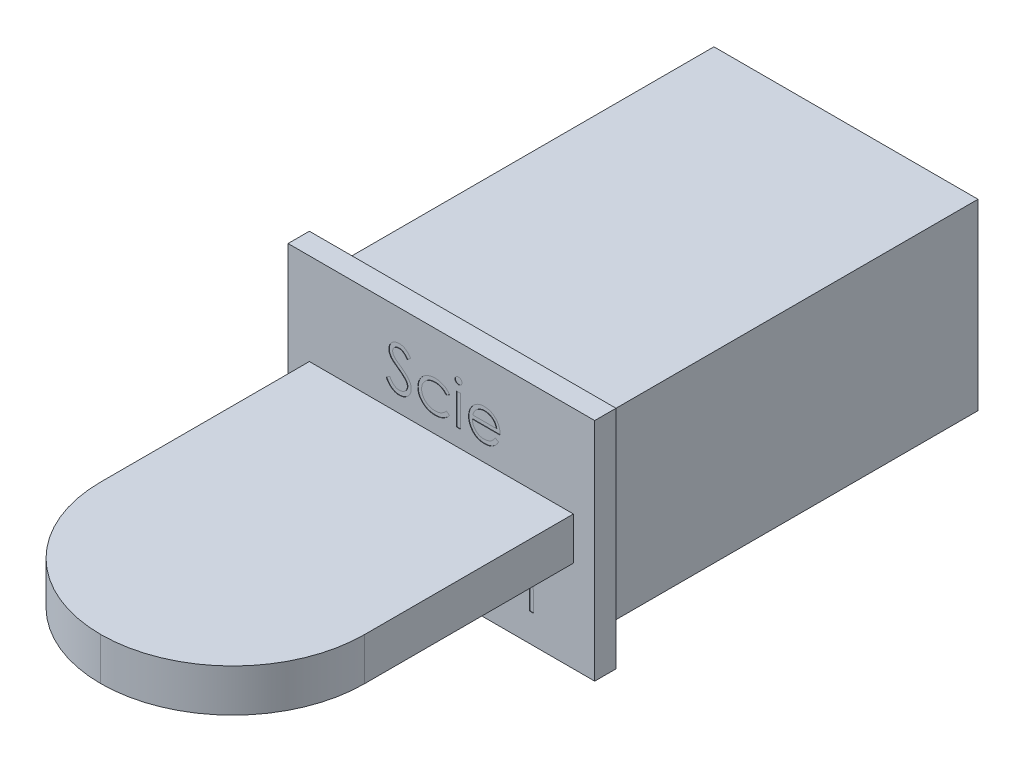
SolidWorks part; units mm, degrees
ref_plane "Front" through (0, 0, 0) normal (0, 0, 1) x (1, 0, 0)
ref_plane "Top" through (0, 0, 0) normal (0, 1, 0) x (1, 0, 0)
ref_plane "Right" through (0, 0, 0) normal (1, 0, 0) x (0, 0, -1)
sketch "Esquisse1" plane through (0, 0, 0) normal (0, 0, 1) x (1, 0, 0)
  line L1 (0, 0) -> (720, 0)
  line L2 (0, 0) -> (0, 530)
  line L3 (0, 530) -> (720, 530)
  line L4 (720, 0) -> (720, 530)
  dimension "D1" = 720
  dimension "D2" = 530
extrude "Boss.-Extru.1" add sketch "Esquisse1" along normal blind 50
sketch "Esquisse2" plane through (0, 0, 0) normal (0, 0, -1) x (-1, 0, 0)
  line L0 (-360, 480) -> (-360, 530) construction
  line L1 (-670, 480) -> (-50, 480)
  line L2 (-670, 480) -> (-670, 50)
  line L3 (-670, 50) -> (-50, 50)
  line L4 (-50, 480) -> (-50, 50)
  line L5 (-720, 530) -> (0, 530) construction
  line L6 (0, 0) -> (-720, 0) construction
  line L9 (-50, 265) -> (0, 265) construction
  line L10 (0, 530) -> (0, 0) construction
  dimension "D1" = 50
extrude "Boss.-Extru.2" add sketch "Esquisse2" along normal blind 900
sketch "Esquisse3" plane through (0, 0, 50) normal (0, 0, 1) x (1, 0, 0)
  line L0 (670, 265) -> (720, 265) construction
  line L1 (50, 215) -> (670, 215)
  line L2 (50, 215) -> (50, 315)
  line L3 (50, 315) -> (670, 315)
  line L4 (670, 215) -> (670, 315)
  line L5 (720, 0) -> (720, 530) construction
  line L6 (360, 215) -> (360, 530) construction
  line L7 (720, 530) -> (0, 530) construction
  dimension "D1" = 50
  dimension "D2" = 100
extrude "Boss.-Extru.3" add sketch "Esquisse3" along normal blind 800
fillet "Congé1" radius 310 2 edges at (670, 265, 850) (50, 265, 850)
sketch "Esquisse4" plane through (0, 0, 50) normal (0, 0, 1) x (1, 0, 0)
  text T0 "Scie" font "Century Gothic" height 100
  text T1 "Ruban" font "Century Gothic" height 100
extrude "Enlèv. mat.-Extru.1" cut sketch "Esquisse4" against normal blind 1
